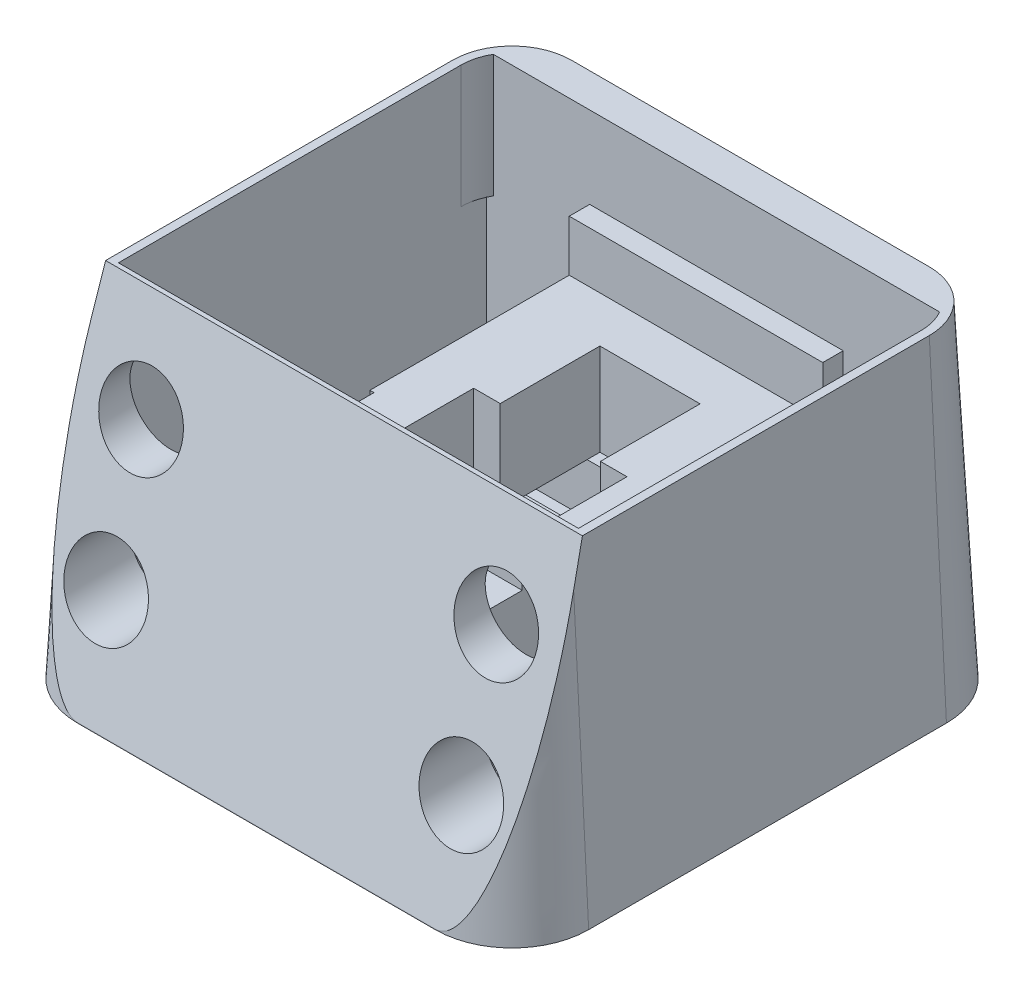
SolidWorks part; units mm, degrees
material "PLA (3D Printing)"
ref_plane "Front Plane" through (0, 0, 0) normal (0, 0, 1) x (1, 0, 0)
ref_plane "Top Plane" through (0, 0, 0) normal (0, 1, 0) x (1, 0, 0)
ref_plane "Right Plane" through (0, 0, 0) normal (1, 0, 0) x (0, 0, -1)
sketch "Sketch1" plane through (0, 0, 0) normal (0, 1, 0) x (1, 0, 0)
  line L0 (-35, 50) -> (35, 50)
  line L5 (50, 35) -> (50, -35)
  line L6 (-50, 35) -> (-50, -35)
  line L7 (-35, -50) -> (35, -50)
  arc A0 (35, -50) -> (50, -35) centre (35, -35) ccw
  arc A1 (-50, -35) -> (-35, -50) centre (-35, -35) ccw
  arc A2 (-50, 35) -> (-35, 50) centre (-35, 35) cw
  arc A3 (35, 50) -> (50, 35) centre (35, 35) cw
  point P14 (0, -50)
  point P19 (-50, 0)
  dimension "D3" = 15
  dimension "D4" = 15
  dimension "D5" = 15
  dimension "D6" = 15
  dimension "D1" = 100
  dimension "D2" = 100
extrude "Boss-Extrude1" add sketch "Sketch1" along normal blind 10
sketch "Sketch2" plane through (0, 10, 0) normal (0, 1, 0) x (1, 0, 0)
  line L0 (-50, 35) -> (-50, -35) construction
  line L1 (-42, 40) -> (-24.8, 40)
  line L2 (-42, 40) -> (-42, -3)
  line L3 (-42, -3) -> (-24.8, -3)
  line L4 (-24.8, 40) -> (-24.8, -3)
  line L5 (-42, 40) -> (-24.8, -3) construction
  line L6 (-42, -3) -> (-24.8, 40) construction
  line L7 (24.8, 40) -> (42, 40)
  line L8 (24.8, 40) -> (24.8, -3)
  line L9 (24.8, -3) -> (42, -3)
  line L10 (42, 40) -> (42, -3)
  line L11 (24.8, 40) -> (42, -3) construction
  line L12 (24.8, -3) -> (42, 40) construction
  line L13 (50, -35) -> (50, 35) construction
  line L15 (35, 50) -> (-35, 50) construction
  point P0 (-33.4, 18.5)
  point P5 (33.4, 18.5)
  dimension "D1" = 8
  dimension "D2" = 8
  dimension "D3" = 17.2
  dimension "D4" = 17.2
  dimension "D5" = 43
  dimension "D6" = 43
  dimension "D7" = 10
  dimension "D8" = 10
extrude "Cut-Extrude1" cut sketch "Sketch2" against normal through all
sketch "Sketch3" plane through (0, 10, 0) normal (0, 1, 0) x (1, 0, 0)
  line L1 (-40, -8) -> (40, -8)
  line L2 (-40, -8) -> (-40, -32)
  line L3 (-40, -32) -> (40, -32)
  line L4 (40, -8) -> (40, -32)
  line L5 (-40, -8) -> (40, -32) construction
  line L6 (-40, -32) -> (40, -8) construction
  line L7 (-45, -3) -> (45, -3)
  line L8 (-45, -3) -> (-45, -37)
  line L9 (-45, -37) -> (45, -37)
  line L10 (45, -3) -> (45, -37)
  line L11 (-45, -3) -> (45, -37) construction
  line L12 (-45, -37) -> (45, -3) construction
  line L13 (-35, -50) -> (35, -50) construction
  line L14 (-42, -3) -> (-24.8, -3) construction
  point P0 (0, -20)
  point P5 (0, -20)
  point P18 (0, -50)
  dimension "D1" = 24
  dimension "D2" = 80
  dimension "D3" = 34
  dimension "D4" = 90
extrude "Boss-Extrude3" add sketch "Sketch3" along normal blind 15
sketch "Sketch4" plane through (0, 10, 0) normal (0, 1, 0) x (1, 0, 0)
  line L0 (24.8, 40) -> (24.8, -3) construction
  line L3 (-24.8, 12.5) -> (24.8, 12.5)
  line L5 (-24.8, 24.5) -> (24.8, 24.5)
  line L6 (-24.8, 29.5) -> (24.8, 29.5)
  line L11 (-24.8, 7.5) -> (24.8, 7.5)
  line L12 (-24.8, 29.5) -> (-24.8, 24.5)
  line L13 (-24.8, -3) -> (-24.8, 40) construction
  line L14 (-24.8, 12.5) -> (-24.8, 7.5)
  line L15 (24.8, 12.5) -> (24.8, 7.5)
  line L16 (24.8, 29.5) -> (24.8, 24.5)
  point P4 (-24.8, 18.5)
  dimension "D1" = 5
  dimension "D2" = 12
  dimension "D3" = 5
  dimension "D4" = 6
extrude "Boss-Extrude4" add sketch "Sketch4" along normal blind 10
sketch "Sketch5" plane through (0, 20, 0) normal (0, 1, 0) x (1, 0, 0)
  line L0 (-24.8, 7.5) -> (24.8, 7.5) construction
  line L1 (-24.8, 29.5) -> (-9.8, 29.5)
  line L2 (-24.8, 29.5) -> (-24.8, 7.5)
  line L3 (-24.8, 7.5) -> (-9.8, 7.5)
  line L4 (-9.8, 29.5) -> (-9.8, 7.5)
  line L6 (24.8, 29.5) -> (9.8, 29.5)
  line L7 (24.8, 29.5) -> (24.8, 7.5)
  line L8 (24.8, 7.5) -> (9.8, 7.5)
  line L9 (9.8, 29.5) -> (9.8, 7.5)
  dimension "D1" = 15
  dimension "D2" = 15
extrude "Boss-Extrude5" add sketch "Sketch5" along normal blind 5
sketch "Sketch6" plane through (0, 10, 0) normal (0, 1, 0) x (1, 0, 0)
  line L1 (-45, -37) -> (45, -37)
  line L2 (-45, -37) -> (-45, 40)
  line L3 (-45, 40) -> (45, 40)
  line L4 (45, -37) -> (45, 40)
  line L5 (45, -37) -> (45, -3) construction
  line L6 (-24.8, 40) -> (-42, 40) construction
  line L7 (-50, 35) -> (-50, -35) construction
  line L8 (-35, -50) -> (35, -50) construction
  line L9 (50, -35) -> (50, 35) construction
  line L10 (35, 50) -> (-35, 50) construction
  line L11 (-50, 35) -> (-50, -35)
  line L12 (-35, -50) -> (35, -50)
  line L13 (50, -35) -> (50, 35)
  line L14 (35, 50) -> (-35, 50)
  arc A0 (-50, -35) -> (-35, -50) centre (-35, -35) ccw construction
  arc A1 (35, -50) -> (50, -35) centre (35, -35) ccw construction
  arc A2 (50, 35) -> (35, 50) centre (35, 35) ccw construction
  arc A3 (-35, 50) -> (-50, 35) centre (-35, 35) ccw construction
  arc A4 (-50, -35) -> (-35, -50) centre (-35, -35) ccw
  arc A5 (35, -50) -> (50, -35) centre (35, -35) ccw
  arc A6 (50, 35) -> (35, 50) centre (35, 35) ccw
  arc A7 (-35, 50) -> (-50, 35) centre (-35, 35) ccw
extrude "Boss-Extrude6" add sketch "Sketch6" along normal up to surface (15 mm away) up to face at (0, 25, 20)
sketch "Sketch9" plane through (0, 25, 0) normal (0, 1, 0) x (1, 0, 0)
  line L22 (-50, 35) -> (-50, -35) construction
  line L23 (-35, -50) -> (35, -50) construction
  line L24 (50, -35) -> (50, 35) construction
  line L25 (35, 50) -> (-35, 50) construction
  line L26 (-45, 35) -> (-45, -35)
  line L27 (-35, -45) -> (35, -45)
  line L28 (45, -35) -> (45, 35)
  line L29 (35, 45) -> (-35, 45)
  line L30 (-45, 35) -> (-45, -32)
  line L32 (45, -32) -> (45, 35)
  line L34 (-50, 35) -> (-50, -35)
  line L35 (-35, -50) -> (35, -50)
  line L36 (50, -35) -> (50, 35)
  line L37 (35, 50) -> (-35, 50)
  line L38 (45, -32) -> (-45, -32)
  line L39 (-40, -32) -> (40, -32) construction
  line L40 (43.6603, 40) -> (-43.6603, 40)
  line L41 (45, 40) -> (-45, 40) construction
  arc A23 (-50, -35) -> (-35, -50) centre (-35, -35) ccw construction
  arc A24 (35, -50) -> (50, -35) centre (35, -35) ccw construction
  arc A25 (50, 35) -> (35, 50) centre (35, 35) ccw construction
  arc A26 (-35, 50) -> (-50, 35) centre (-35, 35) ccw construction
  arc A27 (-45, -35) -> (-35, -45) centre (-35, -35) ccw
  arc A28 (35, -45) -> (45, -35) centre (35, -35) ccw
  arc A29 (45, 35) -> (35, 45) centre (35, 35) ccw
  arc A30 (-35, 45) -> (-45, 35) centre (-35, 35) ccw
  arc A33 (45, 35) -> (43.6603, 40) centre (35, 35) ccw
  arc A34 (-43.6603, 40) -> (-45, 35) centre (-35, 35) ccw
  arc A35 (-50, -35) -> (-35, -50) centre (-35, -35) ccw
  arc A36 (35, -50) -> (50, -35) centre (35, -35) ccw
  arc A37 (50, 35) -> (35, 50) centre (35, 35) ccw
  arc A38 (-35, 50) -> (-50, 35) centre (-35, 35) ccw
  dimension "D1" = 5
extrude "Boss-Extrude8" add sketch "Sketch9" along normal blind 39
chamfer "Chamfer1" distance 64 angle 3 8 edges at (0, 64, 50) (45.6066, 64, 45.6066) (-45.6066, 64, 45.6066) (50, 64, 0) (-50, 64, 0) (45.6066, 64, -45.6066) (-45.6066, 64, -45.6066) (0, 64, -50) first distance on face at (0, 32, 50) first distance on face at (44.0533, 32, 44.0533) first distance on face at (-44.0533, 32, 44.0533) first distance on face at (50, 32, 0) first distance on face at (-50, 32, 0) first distance on face at (44.0533, 32, -44.0533) first distance on face at (-44.0533, 32, -44.0533) first distance on face at (0, 32, -50)
chamfer "Chamfer3" distance 64 angle 12 1 edges at (0, 64, 46.6459) tangent propagation no first distance on face at (0, 32, 48.323)
sketch "Sketch17" plane through (0, 0, -29.5) normal (0, 0, -1) x (-1, 0, 0)
  line L8 (-9.8, 25) -> (-24.8, 25)
  line L9 (-24.8, 10) -> (24.8, 10)
  line L10 (-24.8, 10) -> (24.8, 10)
  line L11 (24.8, 10) -> (24.8, 25)
  line L12 (24.8, 25) -> (9.8, 25)
  line L13 (9.8, 25) -> (9.8, 20)
  line L14 (9.8, 20) -> (-9.8, 20)
  line L15 (-9.8, 20) -> (-9.8, 25)
  line L16 (-9.8, 25) -> (-24.8, 25)
  line L20 (24.8, 25) -> (9.8, 25)
  line L21 (9.8, 25) -> (9.8, 20)
  line L22 (9.8, 20) -> (-9.8, 20)
  line L23 (-9.8, 20) -> (-9.8, 25)
  line L24 (24.8, 10) -> (24.8, 25)
  line L25 (-24.8, 25) -> (-24.8, 10)
  line L26 (-24.8, 25) -> (-24.8, 10)
  dimension "D1" = 0
extrude "Cut-Extrude6" cut sketch "Sketch17" against normal blind 2.5
sketch "Sketch20" plane through (0, 25, 0) normal (0, -1, 0) x (1, 0, 0)
  line L0 (-45, -35) -> (-45, -40) construction
  line L1 (-45, -40) -> (-43.6603, -40) construction
  line L2 (45, -40) -> (45, -35) construction
  line L3 (43.6603, -40) -> (45, -40) construction
  line L4 (-45, -35) -> (-45, -40)
  line L5 (-45, -40) -> (-43.6603, -40)
  line L6 (45, -40) -> (45, -35)
  line L7 (43.6603, -40) -> (45, -40)
  arc A0 (-45, -35) -> (-43.6603, -40) centre (-35, -35) ccw construction
  arc A1 (43.6603, -40) -> (45, -35) centre (35, -35) ccw construction
  arc A2 (-45, -35) -> (-43.6603, -40) centre (-35, -35) ccw
  arc A3 (43.6603, -40) -> (45, -35) centre (35, -35) ccw
extrude "Cut-Extrude8" cut sketch "Sketch20" against normal blind 15
sketch "Sketch21" plane through (0, 25, 0) normal (0, 1, 0) x (1, 0, 0)
  line L4 (40, -8) -> (40, -32)
  line L6 (40, -8) -> (40, -32)
  line L8 (40, -32) -> (45, -32)
  line L10 (40, -32) -> (45, -32)
  line L24 (45, -32) -> (45, -3)
  line L25 (45, -32) -> (45, -3)
  line L26 (45, -3) -> (-45, -3)
  line L27 (45, -3) -> (-45, -3)
  line L28 (-45, -3) -> (-45, -32)
  line L29 (-45, -3) -> (-45, -32)
  line L30 (-45, -32) -> (-40, -32)
  line L31 (-45, -32) -> (-40, -32)
  line L32 (-40, -32) -> (-40, -8)
  line L33 (-40, -32) -> (-40, -8)
  line L34 (-40, -8) -> (40, -8)
  line L35 (-40, -8) -> (40, -8)
  dimension "D1" = 0
extrude "Cut-Extrude9" cut sketch "Sketch21" against normal up to surface (15 mm away) up to face at (0, 10, 20)
sketch "Sketch22" plane through (0, 0, 0) normal (0, -1, 0) x (1, 0, 0)
  line L0 (-35, 50) -> (35, 50) construction
  line L1 (-15, 32) -> (15, 32)
  line L2 (-15, 32) -> (-15, 25)
  line L3 (-15, 25) -> (15, 25)
  line L4 (15, 32) -> (15, 25)
  line L5 (24.8, 3) -> (42, 3) construction
  line L7 (0, 50) -> (0, -50) construction
  line L8 (35, -50) -> (-35, -50) construction
  point P12 (0, 32)
  dimension "D1" = 18
  dimension "D2" = 22
  dimension "D3" = 30
extrude "Cut-Extrude10" cut sketch "Sketch22" against normal up to surface (10 mm away) up to face at (0, 10, -18.5)
sketch "Sketch25" plane through (0, 0, 32) normal (0, 0, -1) x (-1, 0, 0)
  line L0 (-15, 10) -> (-45, 10) construction
  line L1 (45, 10) -> (15, 10) construction
  line L2 (-45, 64) -> (-45, 10) construction
  line L3 (45, 64) -> (45, 10) construction
  circle A0 centre (-34.75, 45.5) radius 8
  circle A1 centre (34.75, 45.5) radius 8
  circle A2 centre (-34.75, 20) radius 8
  circle A3 centre (34.75, 20) radius 8
  dimension "D3" = 16
  dimension "D4" = 16
  dimension "D5" = 16
  dimension "D6" = 16
  dimension "D9" = 10.25
  dimension "D1" = 25.5
  dimension "D2" = 25.5
  dimension "D7" = 10
  dimension "D8" = 10
  dimension "D10" = 10.25
extrude "Cut-Extrude19" cut sketch "Sketch25" against normal through all
sketch "Sketch29" plane through (0, 10, 0) normal (0, 1, 0) x (1, 0, 0)
  line L1 (-24, -3) -> (-15, -3)
  line L2 (-24, -3) -> (-24, -32)
  line L3 (-24, -32) -> (-15, -32)
  line L4 (-15, -3) -> (-15, -32)
  line L5 (15, -32) -> (24, -32)
  line L6 (15, -32) -> (15, -3)
  line L7 (15, -3) -> (24, -3)
  line L8 (24, -32) -> (24, -3)
  line L9 (-45, 40) -> (-45, -32) construction
  line L10 (45, -32) -> (45, 40) construction
  line L11 (-24.8, -3) -> (-42, -3) construction
  line L12 (42, -3) -> (24.8, -3) construction
  line L13 (-45, -32) -> (45, -32) construction
  dimension "D1" = 21
  dimension "D2" = 21
  dimension "D3" = 9
  dimension "D4" = 9
extrude "Boss-Extrude10" add sketch "Sketch29" along normal blind 28
sketch "Sketch31" plane through (0, 10, 0) normal (0, 1, 0) x (1, 0, 0)
  line L4 (24.8, 27) -> (24.8, 40)
  line L6 (24.8, 27) -> (24.8, 40)
  line L13 (24.8, 40) -> (-24.8, 40)
  line L15 (24.8, 40) -> (-24.8, 40)
  line L17 (-24.8, 40) -> (-24.8, 27)
  line L18 (-24.8, 40) -> (-24.8, 27)
  line L19 (-24.8, 27) -> (24.8, 27)
  line L21 (-24.8, 27) -> (24.8, 27)
  dimension "D1" = 0
extrude "Boss-Extrude12" add sketch "Sketch31" along normal up to surface (28 mm away) up to face at (-19.5, 38, 17.5)
sketch "Sketch30" plane through (0, 38, 0) normal (0, 1, 0) x (1, 0, 0)
  line L1 (-24.8, 36) -> (24.8, 36)
  line L2 (-24.8, 36) -> (-24.8, 40)
  line L3 (-24.8, 40) -> (24.8, 40)
  line L11 (-24, -3) -> (-24, -32) construction
  line L12 (-24, -22) -> (24, -22)
  line L13 (-24, -22) -> (-24, -18)
  line L14 (-24, -18) -> (24, -18)
  line L15 (24, -22) -> (24, -18)
  line L16 (24, -3) -> (24, -32) construction
  line L21 (43.6603, 40) -> (-43.6603, 40) construction
  line L22 (-24.8, 40) -> (-24.8, 27) construction
  line L23 (24.8, 40) -> (24.8, 36)
  line L24 (24.8, 27) -> (24.8, 40) construction
  dimension "D1" = 54
  dimension "D2" = 4
  dimension "D3" = 4
extrude "Boss-Extrude11" add sketch "Sketch30" along normal blind 10
sketch "Sketch33" plane through (0, 25, 0) normal (0, 1, 0) x (1, 0, 0)
  line L0 (24.8, 27) -> (9.8, 27) construction
  line L1 (9.8, 27) -> (9.8, 7.5) construction
  line L2 (9.8, 7.5) -> (24.8, 7.5) construction
  line L3 (24.8, 7.5) -> (24.8, 27) construction
  line L4 (-9.8, 7.5) -> (-9.8, 27) construction
  line L5 (-9.8, 27) -> (-24.8, 27) construction
  line L6 (-24.8, 27) -> (-24.8, 7.5) construction
  line L7 (-24.8, 7.5) -> (-9.8, 7.5) construction
  line L8 (24.8, 27) -> (9.8, 27)
  line L9 (9.8, 27) -> (9.8, 7.5)
  line L10 (9.8, 7.5) -> (24.8, 7.5)
  line L11 (24.8, 7.5) -> (24.8, 27)
  line L12 (-9.8, 7.5) -> (-9.8, 27)
  line L13 (-9.8, 27) -> (-24.8, 27)
  line L14 (-24.8, 27) -> (-24.8, 7.5)
  line L15 (-24.8, 7.5) -> (-9.8, 7.5)
extrude "Boss-Extrude13" add sketch "Sketch33" along normal up to surface (13 mm away) up to face at (0, 38, -31.5)
sketch "Sketch23" plane through (0, 10, 0) normal (0, 1, 0) x (1, 0, 0)
  line L1 (-15, -3) -> (15, -3)
  line L2 (-15, -3) -> (-15, -31.9954)
  line L3 (-15, -31.9954) -> (15, -31.9954)
  line L4 (15, -3) -> (15, -31.9954)
  line L6 (0, 50) -> (0, -49.9954) construction
  line L8 (35, -49.9954) -> (-35, -49.9954) construction
  line L12 (35, 50) -> (-35, 50) construction
  line L13 (24, -3) -> (15, -3) construction
  point P8 (0, -3)
  dimension "D2" = 30
  dimension "D3" = 18
extrude "Cut-Extrude17" cut sketch "Sketch23" against normal blind 5
sketch "Sketch34" plane through (0, 10, 0) normal (0, 1, 0) x (1, 0, 0)
  line L1 (-24.8, -3) -> (-15, -3)
  line L2 (-24.8, -3) -> (-24.8, 7.5)
  line L3 (-24.8, 7.5) -> (-15, 7.5)
  line L4 (-15, -3) -> (-15, 7.5)
  line L5 (-24.8, 7.5) -> (24.8, 7.5) construction
  line L6 (24.8, -3) -> (15, -3)
  line L7 (24.8, -3) -> (24.8, 7.5)
  line L8 (24.8, 7.5) -> (15, 7.5)
  line L9 (15, -3) -> (15, 7.5)
  line L10 (-24.8, 7.5) -> (-9.8, 7.5) construction
  line L11 (-15, -18) -> (-15, -3) construction
  line L12 (15, -25) -> (15, -3) construction
extrude "Boss-Extrude14" add sketch "Sketch34" along normal up to surface (28 mm away) up to face at (-19.5, 38, 10.5)
sketch "Sketch35" plane through (0, 10, 0) normal (0, 1, 0) x (1, 0, 0)
  line L4 (15, -3) -> (15, 7.5)
  line L6 (15, -3) -> (15, 7.5)
  line L12 (15, 7.5) -> (-15, 7.5)
  line L14 (15, 7.5) -> (-15, 7.5)
  line L16 (-15, 7.5) -> (-15, -3)
  line L17 (-15, 7.5) -> (-15, -3)
  line L18 (-15, -3) -> (15, -3)
  line L19 (-15, -3) -> (15, -3)
  dimension "D1" = 0
extrude "Cut-Extrude22" cut sketch "Sketch35" against normal up to surface (5 mm away) up to face at (0, 5, 14)
sketch "Sketch37" plane through (0, 5, 0) normal (0, 1, 0) x (1, 0, 0)
  line L4 (-15, -25) -> (15, -25)
  line L5 (15, -25) -> (15, 7.5)
  line L6 (15, 7.5) -> (-15, 7.5)
  line L7 (-15, 7.5) -> (-15, -25)
  line L8 (-15, -25) -> (15, -25)
  line L9 (15, -25) -> (15, 7.5)
  line L10 (15, 7.5) -> (-15, 7.5)
  line L11 (-15, 7.5) -> (-15, -25)
  dimension "D1" = 0
extrude "Boss-Extrude15" add sketch "Sketch37" along normal blind 5
